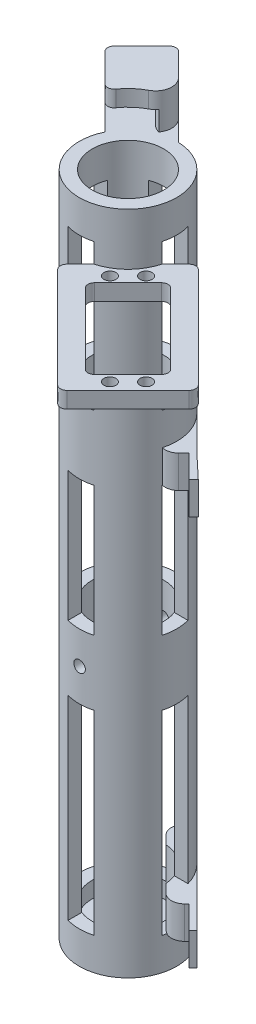
SolidWorks part; units mm, degrees
ref_plane "Front Plane" through (0, 0, 0) normal (0, 0, 1) x (1, 0, 0)
ref_plane "Top Plane" through (0, 0, 0) normal (0, 1, 0) x (1, 0, 0)
ref_plane "Right Plane" through (0, 0, 0) normal (1, 0, 0) x (0, 0, -1)
sketch "Sketch1" plane through (0, 0, 0) normal (0, 1, 0) x (1, 0, 0)
  circle A0 centre (0, 0) radius 13.97
  circle A1 centre (0, 0) radius 19.05
  dimension "D1" = 27.94
  dimension "D2" = 38.1
extrude "Boss-Extrude1" add sketch "Sketch1" along normal blind 260.35
sketch "Sketch2" plane through (0, 0, 0) normal (0, -1, 0) x (1, 0, 0)
  circle A0 centre (0, 0) radius 13.97
extrude "Boss-Extrude2" add sketch "Sketch2" against normal blind 6.35
ref_plane "Plane1" through (0, 0, 16.51) normal (0, 0, 1) x (1, 0, 0)
sketch "Sketch3" plane through (0, 0, 16.51) normal (0, 0, 1) x (1, 0, 0)
  line L0 (-19.05, 0) -> (19.05, 0) construction
  line L1 (0, 101.6) -> (0, 0) construction
  circle A0 centre (0, 101.6) radius 2.2479
  dimension "D1" = 4.4958
  dimension "D2" = 101.6
extrude "Cut-Extrude1" cut sketch "Sketch3" against normal through all and the other way through all contours A0
sketch "Sketch5" plane through (0, 0, 0) normal (1, 0, 0) x (0, 0, -1)
  line L0 (54.1368, 0) -> (-54.1368, 0) construction
  line L1 (5.08, 12.7) -> (-5.08, 12.7)
  line L2 (5.08, 12.7) -> (5.08, 247.65)
  line L3 (5.08, 247.65) -> (-5.08, 247.65)
  line L4 (-5.08, 12.7) -> (-5.08, 247.65)
  line L5 (19.05, 260.35) -> (-19.05, 260.35) construction
  line L6 (0, 0) -> (0, 12.7) construction
  line L7 (-5.08, 114.3) -> (7.62, 114.3)
  line L8 (-5.08, 88.9) -> (7.62, 88.9)
  line L9 (-5.08, 165.1) -> (5.08, 165.1)
  line L10 (-5.08, 190.5) -> (5.08, 190.5)
  dimension "D1" = 12.7
  dimension "D2" = 12.7
  dimension "D3" = 10.16
  dimension "D4" = 12.7
  dimension "D5" = 12.7
  dimension "D6" = 76.2
  dimension "D7" = 25.4
  dimension "D8" = 25.4
  dimension "D9" = 50.8
extrude "Cut-Extrude5" cut sketch "Sketch5" against normal through all both and the other way through all contours L8 L4 L1 L2 | L9 L4 L7 L2 | L4 L10 L2 L3
sketch "Sketch8" plane through (0, 0, 0) normal (0, 0, 1) x (1, 0, 0)
  line L0 (-19.05, 0) -> (19.05, 0) construction
  line L1 (5.08, 12.7) -> (-5.08, 12.7)
  line L2 (5.08, 12.7) -> (5.08, 247.65)
  line L3 (5.08, 247.65) -> (-5.08, 247.65)
  line L4 (-5.08, 12.7) -> (-5.08, 247.65)
  line L5 (19.05, 260.35) -> (-19.05, 260.35) construction
  line L6 (0, 12.7) -> (0, 0) construction
  line L7 (5.08, 88.9) -> (-5.08, 88.9)
  line L8 (5.08, 114.3) -> (-5.08, 114.3)
  line L9 (5.08, 165.1) -> (-5.08, 165.1)
  line L10 (5.08, 190.5) -> (-5.08, 190.5)
  dimension "D1" = 12.7
  dimension "D2" = 10.16
  dimension "D3" = 12.7
  dimension "D4" = 76.2
  dimension "D5" = 25.4
  dimension "D6" = 25.4
  dimension "D7" = 50.8
extrude "Cut-Extrude6" cut sketch "Sketch8" against normal through all both and the other way through all contours L2 L7 L4 L1 | L2 L9 L4 L8 | L10 L2 L3 L4
sketch "Sketch7" plane through (0, 6.35, 0) normal (0, 1, 0) x (1, 0, 0)
  circle A0 centre (0, 0) radius 6.35
extrude "Cut-Extrude4" cut sketch "Sketch7" against normal through all
ref_plane "Plane2" through (11.7201, 0, 11.7201) normal (0.7071, 0, 0.7071) x (0.7071, 0, -0.7071)
sketch "Sketch9" plane through (11.7201, 0, 11.7201) normal (0.7071, 0, 0.7071) x (0.7071, 0, -0.7071)
  line L0 (-19.431, 240.002) -> (19.431, 240.002)
  line L1 (-19.431, 240.002) -> (-19.431, 233.652)
  line L2 (19.431, 240.002) -> (19.431, 233.652)
  line L3 (-19.431, 233.652) -> (19.431, 233.652)
  line L4 (-9.3905, 247.65) -> (9.3905, 247.65) construction
  line L5 (0, 247.65) -> (0, 233.652) construction
  line L8 (9.5, 240.002) -> (-9.5, 240.002) construction
  dimension "D1" = 38.862
  dimension "D2" = 6.35
extrude "Boss-Extrude3" add sketch "Sketch9" along normal blind 8.89
sketch "Sketch10" plane through (18.0063, 0, 18.0063) normal (0.7071, 0, 0.7071) x (0.7071, 0, -0.7071)
  line L0 (-19.431, 240.002) -> (-19.431, 233.652)
  line L1 (-19.431, 240.002) -> (-11.811, 240.002)
  line L2 (-19.431, 233.652) -> (-11.811, 233.652)
  line L3 (-11.811, 240.002) -> (-11.811, 233.652)
  line L4 (19.431, 233.652) -> (19.431, 240.002)
  line L5 (19.431, 233.652) -> (11.811, 233.652)
  line L6 (19.431, 240.002) -> (11.811, 240.002)
  line L7 (11.811, 233.652) -> (11.811, 240.002)
  dimension "D1" = 7.62
  dimension "D2" = 7.62
extrude "Boss-Extrude4" add sketch "Sketch10" along normal blind 51.562
sketch "Sketch11" plane through (-8.3516, 0, 8.3516) normal (0.7071, 0, -0.7071) x (-0.7071, 0, -0.7071)
  line L1 (-77.0267, 240.002) -> (-77.0267, 233.652)
  line L2 (-77.0267, 240.002) -> (-69.4067, 240.002)
  line L3 (-77.0267, 233.652) -> (-69.4067, 233.652)
  line L4 (-69.4067, 240.002) -> (-69.4067, 233.652)
  point P0 (-69.4067, 236.827)
  point P1 (-77.0267, 236.827)
  dimension "D1" = 7.62
extrude "Boss-Extrude5" add sketch "Sketch11" along normal up to next
fillet "Fillet1" radius 2.54 8 edges at (-2.0197, 236.827, 25.4599) (25.4599, 236.827, -2.0197) (40.7263, 236.827, 68.2059) (68.2059, 236.827, 40.7263) (26.3579, 236.827, 9.6546) (57.4296, 236.827, 40.7263) (9.6546, 236.827, 26.3579) (40.7263, 236.827, 57.4296)
sketch "Sketch12" plane through (0, 240.002, 0) normal (0, 1, 0) x (1, 0, 0)
  circle A0 centre (48.0338, -55.1048) radius 2.3559
  circle A1 centre (55.1048, -48.0338) radius 2.3559
  circle A2 centre (19.2545, -12.1834) radius 2.3558
  circle A3 centre (12.1834, -19.2545) radius 2.3558
  dimension "D1" = 4.7117
extrude "Cut-Extrude7" cut sketch "Sketch12" against normal up to next
ref_plane "Plane4" through (-13.4704, 0, -13.4704) normal (-0.7071, 0, -0.7071) x (-0.7071, 0, 0.7071)
sketch "Sketch17" plane through (-13.4704, 0, -13.4704) normal (-0.7071, 0, -0.7071) x (-0.7071, 0, 0.7071)
  line L0 (6.35, 260.35) -> (-13.97, 260.35)
  line L1 (6.35, 260.35) -> (6.35, 254)
  line L2 (-13.97, 260.35) -> (-13.97, 254)
  line L3 (6.35, 254) -> (-13.97, 254)
  line L4 (0, 260.35) -> (0, 254) construction
  line L5 (19.05, 260.35) -> (-19.05, 260.35) construction
  line L6 (0, 260.35) -> (0, 246.0215) construction
  dimension "D1" = 6.35
  dimension "D2" = 20.32
  dimension "D3" = 6.35
extrude "Boss-Extrude6" add sketch "Sketch17" along normal blind 20.32 and the other way up to body separate body
sketch "Sketch20" plane through (0, 260.35, 0) normal (0, 1, 0) x (1, 0, 0)
  line L0 (0.7202, 19.0364) -> (-17.9605, 37.7171)
  line L1 (-17.9605, 37.7171) -> (-32.3289, 23.3487)
  line L2 (-32.3289, 23.3487) -> (-17.1901, 8.2099)
  arc A0 (0.7202, 19.0364) -> (-17.1901, 8.2099) centre (0, 0) ccw
extrude "Boss-Extrude8" add sketch "Sketch20" along normal blind 13.97
sketch "Sketch21" plane through (0, 274.32, 0) normal (0, 1, 0) x (1, 0, 0)
  line L0 (-27.8388, 18.8585) -> (-17.9605, 28.7368)
  line L1 (-32.3289, 23.3487) -> (-17.1901, 8.2099) construction
  line L2 (-17.9605, 28.7368) -> (-6.9577, 17.734)
  line L3 (-17.1901, 8.2099) -> (-27.8388, 18.8585)
  line L5 (-17.9605, 37.7171) -> (-32.3289, 23.3487) construction
  line L6 (0.7202, 19.0364) -> (-17.9605, 37.7171) construction
  arc A0 (0.7202, 19.0364) -> (-17.1901, 8.2099) centre (0, 0) ccw construction
  arc A1 (-17.1901, 8.2099) -> (-6.9577, 17.734) centre (0, 0) cw
  dimension "D1" = 6.35
  dimension "D2" = 6.35
extrude "Cut-Extrude8" cut sketch "Sketch21" against normal up to surface (7.62 mm away) from offset 6.35 up to face at (0, 260.35, 13.97) offset against normal yes
fillet "Fillet3" radius 2.54 4 edges at (-17.9605, 264.16, -37.7171) (-27.8388, 264.16, -18.8585) (-32.3289, 264.16, -23.3487) (-17.1901, 271.145, -8.2099)
fillet "Fillet4" radius 6.35 2 edges at (-6.9577, 264.16, -17.734) (0.7202, 267.335, -19.0364)
ref_plane "Plane5" through (0, 25.13, 0) normal (0, -1, 0) x (-1, 0, 0)
ref_plane "Plane9" through (0, 177.8, 0) normal (0, -1, 0) x (-1, 0, 0)
sketch "Sketch23" plane through (0, 177.8, 0) normal (0, -1, 0) x (-1, 0, 0)
  line L0 (0, 0) -> (-13.4704, 13.4704) construction
  line L1 (-26.9408, 0) -> (0, 26.9408)
  line L2 (-20.2056, -6.7352) -> (-14.6041, -1.1337)
  line L3 (-25.4149, -1.5258) -> (-20.2056, -6.7352)
  line L4 (1.7961, 25.1447) -> (6.7352, 20.2056)
  line L5 (1.1337, 14.6041) -> (6.7352, 20.2056)
  line L6 (-26.9408, 0) -> (-36.1864, -8.7068)
  line L7 (-66.4098, -38.9303) -> (-27.2559, 0.2237) construction
  line L8 (-36.1864, -8.7068) -> (-34.445, -10.5559)
  line L9 (-34.445, -10.5559) -> (-25.4149, -1.5258)
  line L10 (0, 26.9408) -> (8.9803, 35.921)
  line L11 (8.9803, 35.921) -> (10.7763, 34.125)
  line L12 (10.7763, 34.125) -> (1.7961, 25.1447)
  arc A0 (1.1337, 14.6041) -> (-14.6041, -1.1337) centre (0, 0) ccw
  circle A2 centre (0, 0) radius 19.05 construction
  point P5 (-11.0367, 16.079)
  point P10 (-13.4704, 13.4704)
  point P13 (-6.7352, 6.7352)
  dimension "D1" = 38.1
  dimension "D2" = 9.525
  dimension "D3" = 12.7
  dimension "D4" = 12.7
  dimension "D5" = 2.54
  dimension "D6" = 2.54
extrude "Boss-Extrude10" add sketch "Sketch23" along normal blind 12.7
fillet "Fillet5" radius 5.08 2 edges at (-6.7352, 171.45, -20.2056) (20.2056, 171.45, 6.7352)
sketch "Sketch24" plane through (12.6625, 0, -13.4461) normal (0.6856, 0, -0.728) x (-0.728, 0, -0.6856)
  circle A0 centre (-26.1369, 171.2262) radius 2.54
  circle A2 centre (24.6631, 171.2262) radius 2.54
  dimension "D1" = 5.08
  dimension "D2" = 5.08
  dimension "D3" = 50.8
  dimension "D4" = 50.8
extrude "Cut-Extrude12" cut sketch "Sketch24" against normal blind 2.54 contours A0
sketch "Sketch25" plane through (11.6743, 0, -11.6743) normal (-0.7071, 0, 0.7071) x (0.7071, 0, 0.7071)
  circle A0 centre (-24.9775, 171.4636) radius 2.54
  dimension "D1" = 5.08
extrude "Cut-Extrude13" cut sketch "Sketch25" against normal blind 2.54
sketch "Sketch26" plane through (0, 25.13, 0) normal (0, -1, 0) x (-1, 0, 0)
  line L0 (0, 0) -> (-13.4704, 13.4704) construction
  line L1 (8.9803, 35.921) -> (-13.4704, 13.4704) construction
  line L2 (-35.921, -8.9803) -> (8.9803, 35.921)
  line L3 (-35.921, -8.9803) -> (-34.445, -10.5559)
  line L4 (-34.445, -10.5559) -> (-25.4149, -1.5258)
  line L5 (-25.4149, -1.5258) -> (-23.3214, -3.6194) construction
  line L6 (-34.445, -10.5559) -> (-25.4149, -1.5258) construction
  line L7 (-25.4149, -1.5258) -> (-20.8999, -6.0409)
  line L8 (-20.8999, -6.0409) -> (-13.9384, 0.9206)
  line L9 (6.0005, 20.8595) -> (1.4855, 25.3746)
  line L10 (1.4855, 25.3746) -> (10.7763, 34.125)
  line L11 (10.7763, 34.125) -> (9.0356, 35.9732)
  line L12 (8.9803, 35.921) -> (9.0356, 35.9732)
  line L13 (-0.9206, 13.9384) -> (6.0005, 20.8595)
  circle A0 centre (0, 0) radius 19.05 construction
  arc A1 (-0.9206, 13.9384) -> (-13.9384, 0.9206) centre (0, 0) ccw
  point P11 (-13.4704, 13.4704)
extrude "Boss-Extrude11" add sketch "Sketch26" along normal blind 12.7
fillet "Fillet6" radius 5.08 2 edges at (-6.0005, 18.78, -20.8595) (20.8999, 18.78, 6.0409)
sketch "Sketch27" plane through (13.4704, 0, -13.4704) normal (0.7071, 0, -0.7071) x (-0.7071, 0, -0.7071)
  line L0 (0, 12.43) -> (-31.75, 12.43) construction
  line L2 (31.75, 12.43) -> (0, 12.43) construction
  line L3 (-31.8205, 12.43) -> (-31.8205, 25.13) construction
  line L4 (31.75, 12.43) -> (31.75, 25.13) construction
  circle A0 centre (-25.4705, 18.78) radius 2.54
  circle A1 centre (25.4, 18.78) radius 2.54
  dimension "D1" = 5.08
  dimension "D3" = 5.08
  dimension "D6" = 6.35
  dimension "D2" = 6.35
  dimension "D4" = 6.35
  dimension "D5" = 6.35
extrude "Cut-Extrude14" cut sketch "Sketch27" against normal blind 12.7
